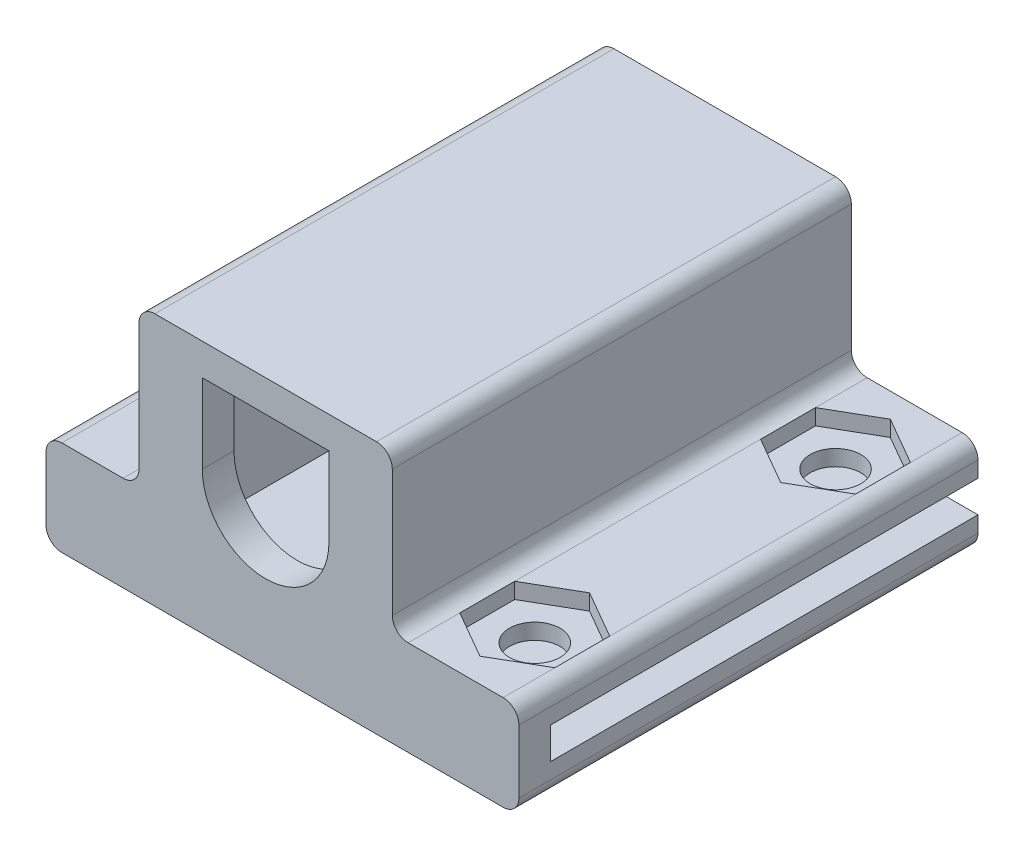
SolidWorks part; units mm, degrees
ref_plane "前视基准面" through (0, 0, 0) normal (0, 0, 1) x (1, 0, 0)
ref_plane "上视基准面" through (0, 0, 0) normal (0, 1, 0) x (1, 0, 0)
ref_plane "右视基准面" through (0, 0, 0) normal (1, 0, 0) x (0, 0, -1)
sketch "草图1" plane through (0, 0, 0) normal (0, 0, 1) x (1, 0, 0)
  line L1 (-12.875, -3) -> (-9, -3)
  line L2 (-13.875, -4) -> (-13.875, -8)
  line L3 (-12.875, -9) -> (15, -9)
  line L4 (5.5, 5) -> (-5.5, 5)
  line L5 (-6, 4.5) -> (-6, -4.5)
  line L6 (-5.5, -5) -> (5.5, -5)
  line L7 (6, -4.5) -> (6, 4.5)
  line L8 (5.5, 5) -> (-5.5, 5)
  line L9 (-6, 4.5) -> (-6, -4.5)
  line L10 (-5.5, -5) -> (5.5, -5)
  line L11 (6, -4.5) -> (6, 4.5)
  line L12 (-11.875, -7) -> (88.125, -7)
  line L13 (88.125, -7) -> (88.125, -5)
  line L14 (88.125, -5) -> (-11.875, -5)
  line L15 (-11.875, -5) -> (-11.875, -7)
  line L16 (-11.875, -7) -> (88.125, -7)
  line L17 (88.125, -7) -> (88.125, -5)
  line L18 (88.125, -5) -> (-11.875, -5)
  line L19 (-11.875, -5) -> (-11.875, -7)
  line L20 (16, -4) -> (16, -8)
  line L21 (-7, 7) -> (7, 7)
  line L22 (-8, 6) -> (-8, -2)
  line L23 (-8, -5) -> (8, -5)
  line L24 (8, 6) -> (8, -2)
  line L25 (9, -3) -> (15, -3)
  line L27 (0.8292, -1.25) -> (0.8292, 1.25)
  line L28 (0.8292, -1.25) -> (0.8292, 1.25)
  line L30 (-4, 0) -> (-4, 5)
  line L31 (-4, 5) -> (4, 5)
  line L32 (4, 0) -> (4, 5)
  arc A0 (-4, 0) -> (4, 0) centre (0, 0) ccw
  arc A1 (0.8292, 1.25) -> (0.8292, -1.25) centre (0, 0) ccw
  arc A2 (0.8292, 1.25) -> (0.8292, -1.25) centre (0, 0) ccw
  arc A3 (-7, 7) -> (-8, 6) centre (-7, 6) ccw
  arc A4 (6, 4.5) -> (5.5, 5) centre (5.5, 4.5) ccw
  arc A5 (-5.5, 5) -> (-6, 4.5) centre (-5.5, 4.5) ccw
  arc A6 (-6, -4.5) -> (-5.5, -5) centre (-5.5, -4.5) ccw
  arc A7 (5.5, -5) -> (6, -4.5) centre (5.5, -4.5) ccw
  arc A8 (6, 4.5) -> (5.5, 5) centre (5.5, 4.5) ccw
  arc A9 (-5.5, 5) -> (-6, 4.5) centre (-5.5, 4.5) ccw
  arc A10 (-6, -4.5) -> (-5.5, -5) centre (-5.5, -4.5) ccw
  arc A11 (5.5, -5) -> (6, -4.5) centre (5.5, -4.5) ccw
  arc A12 (-9, -3) -> (-8, -2) centre (-9, -2) ccw
  arc A13 (-12.875, -3) -> (-13.875, -4) centre (-12.875, -4) ccw
  arc A14 (-12.875, -9) -> (-13.875, -8) centre (-12.875, -8) cw
  arc A15 (15, -9) -> (16, -8) centre (15, -8) ccw
  arc A16 (16, -4) -> (15, -3) centre (15, -4) ccw
  arc A17 (8, -2) -> (9, -3) centre (9, -2) ccw
  arc A18 (8, 6) -> (7, 7) centre (7, 6) ccw
  dimension "D11" = 8
  dimension "D12" = 1
  dimension "D3" = 2
  dimension "D4" = 2
  dimension "D5" = 2
  dimension "D6" = 2
  dimension "D7" = 2
  dimension "D8" = 8
  dimension "D9" = 2
  dimension "D1" = 0
  dimension "D2" = 0
  dimension "D10" = 0
extrude "凸台-拉伸1" add sketch "草图1" along normal blind 2 contours L10 A11 L11 A8 L8 L32 A0 L30 A9 L9 A10 | A11 L18 L20 L25 L24 L21 L22 L1 L2 L3 L16 L19 A10 L9 A9 L8 A8 L11 | L20 L18 L10 L19 L16 region at (-10.9375, -3.3389, 0) region at (2.0625, -6, 0) region at (0, -4.8438, 0)
sketch "草图2" plane through (0, 0, 0) normal (0, 0, -1) x (-1, 0, 0)
  line L0 (-88.125, -5) -> (11.875, -5) construction
  line L1 (-6, 5) -> (6, 5)
  line L2 (-6, 5) -> (-6, -5)
  line L4 (-6, 4.5) -> (-6, -4.5)
  line L5 (-5.5, -5) -> (5.5, -5)
  line L6 (6, -4.5) -> (6, 4.5)
  line L7 (5.5, 5) -> (-5.5, 5)
  line L8 (-16, -4) -> (-16, -8)
  line L9 (-15, -9) -> (12.875, -9)
  line L10 (13.875, -8) -> (13.875, -4)
  line L11 (12.875, -3) -> (9, -3)
  line L12 (8, -2) -> (8, 6)
  line L13 (7, 7) -> (-7, 7)
  line L14 (-8, 6) -> (-8, -2)
  line L15 (-9, -3) -> (-15, -3)
  line L16 (-16, -4) -> (-16, -8)
  line L17 (-15, -9) -> (12.875, -9)
  line L18 (13.875, -8) -> (13.875, -4)
  line L19 (12.875, -3) -> (9, -3)
  line L20 (8, -2) -> (8, 6)
  line L21 (7, 7) -> (-7, 7)
  line L22 (-8, 6) -> (-8, -2)
  line L23 (-9, -3) -> (-15, -3)
  line L24 (-6, 4.5) -> (-6, -4.5)
  line L26 (6, -4.5) -> (6, 4.5)
  line L27 (5.5, 5) -> (-5.5, 5)
  line L28 (6, 5) -> (6, -5)
  line L33 (-6, -5) -> (-88.125, -5)
  line L37 (-88.125, -7) -> (11.875, -7)
  line L38 (-88.125, -5) -> (-88.125, -7)
  line L39 (11.875, -5) -> (-88.125, -5)
  line L40 (11.875, -7) -> (11.875, -5)
  line L41 (-88.125, -7) -> (11.875, -7)
  line L42 (-88.125, -5) -> (-88.125, -7)
  line L43 (11.875, -5) -> (6, -5)
  line L44 (11.875, -7) -> (11.875, -5)
  arc A4 (-5.5, 5) -> (-6, 4.5) centre (-5.5, 4.5) ccw
  arc A5 (-6, -4.5) -> (-5.5, -5) centre (-5.5, -4.5) ccw
  arc A6 (5.5, -5) -> (6, -4.5) centre (5.5, -4.5) ccw
  arc A7 (6, 4.5) -> (5.5, 5) centre (5.5, 4.5) ccw
  arc A8 (-5.5, 5) -> (-6, 4.5) centre (-5.5, 4.5) ccw
  arc A11 (6, 4.5) -> (5.5, 5) centre (5.5, 4.5) ccw
  arc A16 (-16, -8) -> (-15, -9) centre (-15, -8) ccw
  arc A17 (-16, -8) -> (-15, -9) centre (-15, -8) ccw
  arc A18 (12.875, -9) -> (13.875, -8) centre (12.875, -8) ccw
  arc A19 (12.875, -9) -> (13.875, -8) centre (12.875, -8) ccw
  arc A20 (13.875, -4) -> (12.875, -3) centre (12.875, -4) ccw
  arc A21 (13.875, -4) -> (12.875, -3) centre (12.875, -4) ccw
  arc A22 (8, -2) -> (9, -3) centre (9, -2) ccw
  arc A23 (8, -2) -> (9, -3) centre (9, -2) ccw
  arc A24 (8, 6) -> (7, 7) centre (7, 6) ccw
  arc A25 (8, 6) -> (7, 7) centre (7, 6) ccw
  arc A26 (-7, 7) -> (-8, 6) centre (-7, 6) ccw
  arc A27 (-7, 7) -> (-8, 6) centre (-7, 6) ccw
  arc A28 (-9, -3) -> (-8, -2) centre (-9, -2) ccw
  arc A29 (-9, -3) -> (-8, -2) centre (-9, -2) ccw
  arc A30 (-15, -3) -> (-16, -4) centre (-15, -4) ccw
  arc A31 (-15, -3) -> (-16, -4) centre (-15, -4) ccw
  point P26 (6, 0)
  line M20 (-16, -4) -> (-16, -8)
  line M21 (-15, -9) -> (12.875, -9)
  line M22 (13.875, -8) -> (13.875, -4)
  line M23 (12.875, -3) -> (9, -3)
  line M24 (8, -2) -> (8, 6)
  line M25 (7, 7) -> (-7, 7)
  line M26 (-8, 6) -> (-8, -2)
  line M27 (-9, -3) -> (-15, -3)
  line M28 (-4, 5) -> (4, 5)
  dimension "D3" = 0
  dimension "D4" = 0
  dimension "D5" = 0
  dimension "D1" = 0
  dimension "D2" = 0
extrude "凸台-拉伸2" add sketch "草图2" along normal offset from surface (27 mm away) 2 contours L44 L41 L16 L43 L2 L1 L28 L26 M21 M22 M23 M24 M25 M26 M27 M20 M28 region at (6.3389, 4.75, 0) offset beyond the face yes
sketch "草图5" plane through (0, -3, 0) normal (0, 1, 0) x (1, 0, 0)
  line L0 (12, -2) -> (12, 27) construction
  line L4 (15, -2) -> (15, 27)
  line L5 (15, 27) -> (9, 27)
  line L6 (15, -2) -> (15, 27)
  line L7 (9, -2) -> (15, -2)
  line L11 (9, -2) -> (15, -2)
  line L16 (15, 23.7321) -> (12, 25.4641)
  line L17 (12, 25.4641) -> (9, 23.7321)
  line L18 (15, 27) -> (9, 27)
  line L19 (9, 27) -> (9, -2)
  line L20 (9, 27) -> (9, -2)
  line L21 (9, 23.7321) -> (9, 20.2679)
  line L22 (9, 20.2679) -> (12, 18.5359)
  line L23 (12, 18.5359) -> (15, 20.2679)
  line L24 (15, 20.2679) -> (15, 23.7321)
  circle A1 centre (12, 22) radius 3 construction
  dimension "D3" = 5
  dimension "D2" = 6
  dimension "D1" = 0
extrude "切除-拉伸2" cut sketch "草图5" against normal blind 1 and the other way through all contours L21 L22 L23 L24 L16 L17
sketch "草图6" plane through (0, -3, 0) normal (0, 1, 0) x (1, 0, 0)
  line L0 (12, -2) -> (12, 27) construction
  line L1 (15, 27) -> (9, 27) construction
  line L4 (15, 20.2679) -> (12, 18.5359)
  line L5 (12, 18.5359) -> (9, 20.2679)
  line L6 (15, 20.2679) -> (12, 18.5359)
  line L7 (9, -2) -> (15, -2)
  line L11 (9, -2) -> (15, -2)
  line L14 (12, 25.4641) -> (9, 23.7321)
  line L15 (12, 25.4641) -> (9, 23.7321)
  line L16 (9, 23.7321) -> (9, 20.2679)
  line L17 (9, 20.2679) -> (12, 18.5359)
  line L18 (12, 18.5359) -> (15, 20.2679)
  line L19 (15, 20.2679) -> (15, 23.7321)
  line L22 (9, 23.7321) -> (9, 20.2679)
  line L23 (9, 20.2679) -> (12, 18.5359)
  line L24 (12, 18.5359) -> (15, 20.2679)
  line L29 (15, 4.7321) -> (12, 6.4641)
  line L30 (12, 6.4641) -> (9, 4.7321)
  line L32 (9, 4.7321) -> (9, 1.2679)
  line L33 (12, 18.5359) -> (9, 20.2679)
  line L34 (9, 1.2679) -> (12, -0.4641)
  line L35 (15, 20.2679) -> (15, 23.7321)
  line L36 (15, 23.7321) -> (12, 25.4641)
  line L37 (15, 23.7321) -> (12, 25.4641)
  line L38 (9, 20.2679) -> (9, -2)
  line L39 (9, 20.2679) -> (9, -2)
  line L40 (15, -2) -> (15, 20.2679)
  line L41 (15, -2) -> (15, 20.2679)
  line L42 (12, -0.4641) -> (15, 1.2679)
  line L43 (15, 1.2679) -> (15, 4.7321)
  circle A0 centre (12, 3) radius 3 construction
  dimension "D3" = 6
  dimension "D4" = 5
  dimension "D1" = 0
  dimension "D2" = 0
extrude "切除-拉伸3" cut sketch "草图6" against normal blind 1 and the other way through all contours L32 L34 L42 L43 L29 L30
sketch "草图8" plane through (0, 0, -27) normal (0, 0, -1) x (-1, 0, 0)
  line L0 (6, -5) -> (6, 5) construction
  line L1 (-6, 5) -> (6, 5)
  line L2 (-6, 5) -> (-6, 4)
  line L3 (-6, 4) -> (6, 4)
  line L4 (6, 5) -> (6, 4)
  dimension "D1" = 1
extrude "凸台-拉伸3" add sketch "草图8" against normal blind 1.6
sketch "草图9" plane through (0, -4, 0) normal (0, 1, 0) x (1, 0, 0)
  line L0 (9, 4.7321) -> (15, 1.2679) construction
  line L1 (9, 23.7321) -> (15, 20.2679) construction
  line L6 (12, 6.4641) -> (9, 4.7321)
  line L7 (9, 4.7321) -> (9, 1.2679)
  line L8 (9, 1.2679) -> (12, -0.4641)
  line L9 (12, -0.4641) -> (15, 1.2679)
  line L10 (15, 1.2679) -> (15, 4.7321)
  line L11 (15, 4.7321) -> (12, 6.4641)
  line L12 (12, 6.4641) -> (9, 4.7321)
  line L13 (9, 4.7321) -> (9, 1.2679)
  line L14 (9, 1.2679) -> (12, -0.4641)
  line L15 (12, -0.4641) -> (15, 1.2679)
  line L16 (15, 1.2679) -> (15, 4.7321)
  line L17 (15, 4.7321) -> (12, 6.4641)
  line L18 (12, 25.4641) -> (9, 23.7321)
  line L19 (9, 23.7321) -> (9, 20.2679)
  line L20 (9, 20.2679) -> (12, 18.5359)
  line L21 (12, 18.5359) -> (15, 20.2679)
  line L22 (15, 20.2679) -> (15, 23.7321)
  line L23 (15, 23.7321) -> (12, 25.4641)
  line L24 (12, 25.4641) -> (9, 23.7321)
  line L25 (9, 23.7321) -> (9, 20.2679)
  line L26 (9, 20.2679) -> (12, 18.5359)
  line L27 (12, 18.5359) -> (15, 20.2679)
  line L28 (15, 20.2679) -> (15, 23.7321)
  line L29 (15, 23.7321) -> (12, 25.4641)
  circle A0 centre (12, 3) radius 1.6
  circle A1 centre (12, 22) radius 1.6
  dimension "D3" = 3.2
  dimension "D4" = 3.2
  dimension "D1" = 0
  dimension "D2" = 0
extrude "切除-拉伸4" cut sketch "草图9" against normal through all contours A0 | A1 region at (12, -4, -3) region at (12, -4, -22)
